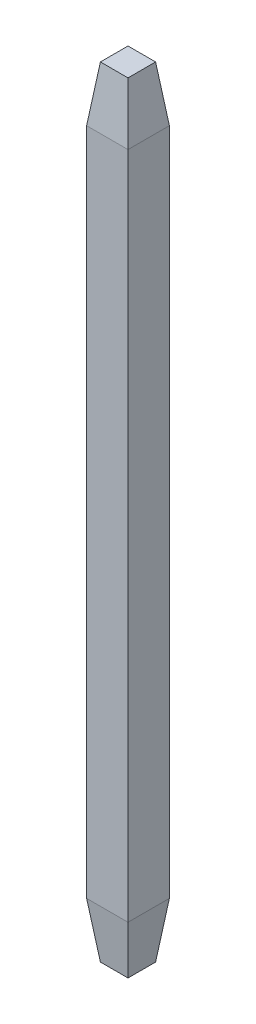
SolidWorks part; units mm, degrees
ref_plane "정면" through (0, 0, 0) normal (0, 0, 1) x (1, 0, 0)
ref_plane "윗면" through (0, 0, 0) normal (0, 1, 0) x (1, 0, 0)
ref_plane "우측면" through (0, 0, 0) normal (1, 0, 0) x (0, 0, -1)
sketch "스케치1" plane through (0, 0, 0) normal (0, 1, 0) x (1, 0, 0)
  line L1 (-0.3, -0.3) -> (0.3, -0.3)
  line L2 (-0.3, -0.3) -> (-0.3, 0.3)
  line L3 (-0.3, 0.3) -> (0.3, 0.3)
  line L4 (0.3, -0.3) -> (0.3, 0.3)
  line L5 (-0.3, -0.3) -> (0.3, 0.3) construction
  line L6 (-0.3, 0.3) -> (0.3, -0.3) construction
  point P0 (0, 0)
  dimension "D1" = 0.6
  dimension "D2" = 0.6
extrude "보스-돌출1" add sketch "스케치1" along normal blind 11.3
chamfer "모따기1" distance 0.8 distance2 0.1 8 edges at (0, 0, -0.3) (-0.3, 0, 0) (0, 0, 0.3) (0.3, 0, 0) (0, 11.3, 0.3) (-0.3, 11.3, 0) (0, 11.3, -0.3) (0.3, 11.3, 0) first distance on face at (0, 5.65, -0.3) first distance on face at (-0.3, 5.65, 0) first distance on face at (0, 5.65, 0.3) first distance on face at (0.3, 5.65, 0)
ref_axis "기준축1" through (0, 10.5, 0) along (0, -1, 0)
